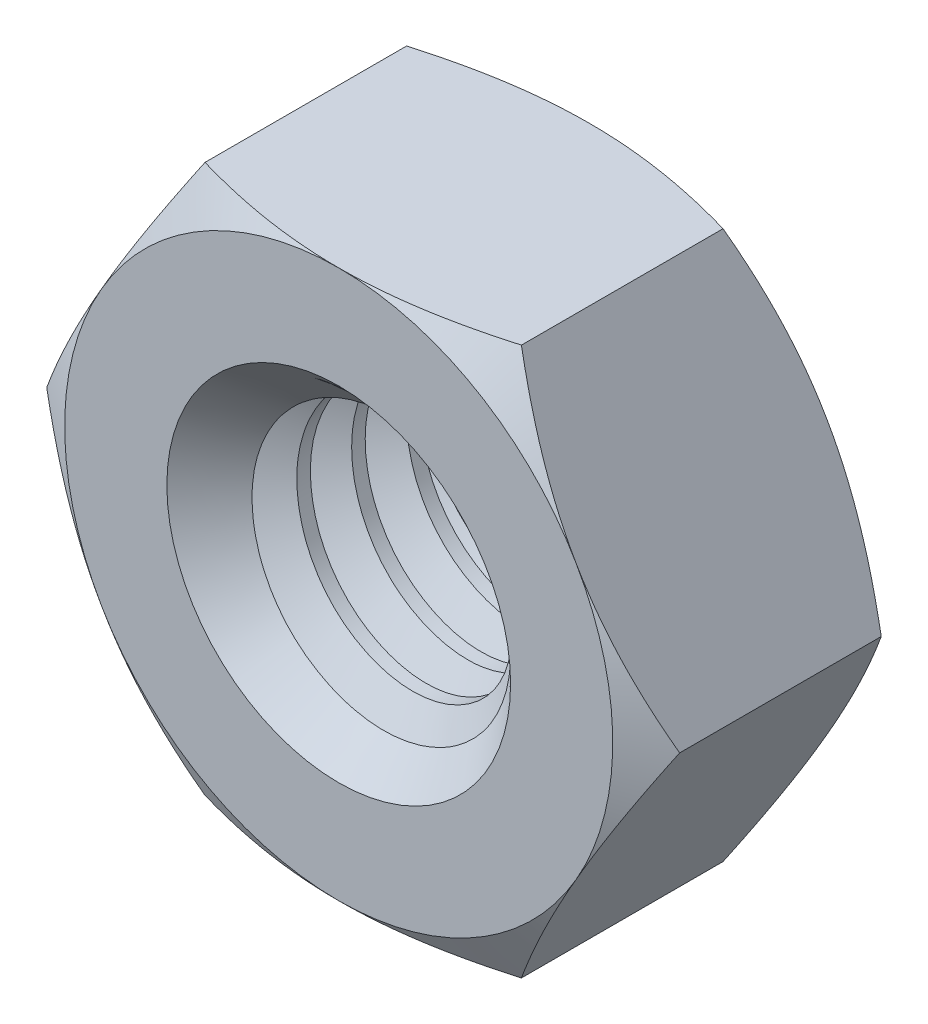
SolidWorks part; units mm, degrees
ref_plane "Front" through (0, 0, 0) normal (0, 0, 1) x (1, 0, 0)
ref_plane "Top" through (0, 0, 0) normal (0, 1, 0) x (1, 0, 0)
ref_plane "Right" through (0, 0, 0) normal (1, 0, 0) x (0, 0, -1)
sketch "Çizim1" plane through (0, 0, 0) normal (0, 0, 1) x (1, 0, 0)
  line L1 (4.0415, 0) -> (2.0207, 3.5)
  line L2 (2.0207, 3.5) -> (-2.0207, 3.5)
  line L3 (-2.0207, 3.5) -> (-4.0415, 0)
  line L4 (-4.0415, 0) -> (-2.0207, -3.5)
  line L5 (-2.0207, -3.5) -> (2.0207, -3.5)
  line L6 (2.0207, -3.5) -> (4.0415, 0)
  circle A0 centre (0, 0) radius 3.5 construction
  point P1 (0, 0)
  dimension "D1" = 7
extrude "Yükseklik-Ekstrüzyon1" add sketch "Çizim1" along normal blind 3.2
sketch "Çizim2" plane through (0, 0, 3.2) normal (0, 0, 1) x (1, 0, 0)
  circle A0 centre (0, 0) radius 3.5
extrude "Kes-Ekstrüzyon1" cut sketch "Çizim2" against normal blind 3.2 draft 60 flip side to cut
sketch "Çizim3" plane through (0, 0, 0) normal (0, 0, -1) x (-1, 0, 0)
  circle A0 centre (0, 0) radius 3.5
extrude "Kes-Ekstrüzyon2" cut sketch "Çizim3" against normal blind 3.2 draft 60 flip side to cut
sketch "Çizim5" plane through (0, 0, 0) normal (0, 0, -1) x (-1, 0, 0)
  circle A0 centre (0, 0) radius 1.545
  dimension "D1" = 3.09
extrude "Kes-Ekstrüzyon3" cut sketch "Çizim5" against normal blind 3.2
chamfer "Pah1" distance 0.65 angle 45 2 edges at (-1.545, 0, 3.2) (-1.545, 0, 0)
sketch "Çizim6" plane through (0, 0, 0) normal (0, 0, -1) x (-1, 0, 0)
  circle A0 centre (0, 0) radius 1.545
curve "Helis/Spiral1" pitch 0.7 height 4 radius 1.545 centre (0, 0, 0) axis (0, 0, 1) start towards (1, 0, 0)
ref_plane "Düzlem1" through (-0.3438, -1.5063, 4) normal (0.9724, -0.2219, 0.0719) x (0.0701, -0.016, -0.9974)
sketch "Çizim7" plane through (-0.3438, -1.5063, 4) normal (0.9724, -0.2219, 0.0719) x (0.0701, -0.016, -0.9974)
  line L0 (0.3473, 0.1465) -> (-0.3473, 0.1465)
  line L1 (0, -0.455) -> (0.3473, 0.1465)
  line L3 (-0.3473, 0.1465) -> (0, -0.455)
  line L5 (0.394, 0.2275) -> (0, 0.2275) [skipped]
  circle A0 centre (0, 0) radius 0.2275 construction
  dimension "D1" = 0.455
sweep "Kes-Süpür1" cut profiles "Çizim7" path "Helis/Spiral1" align with end faces yes
